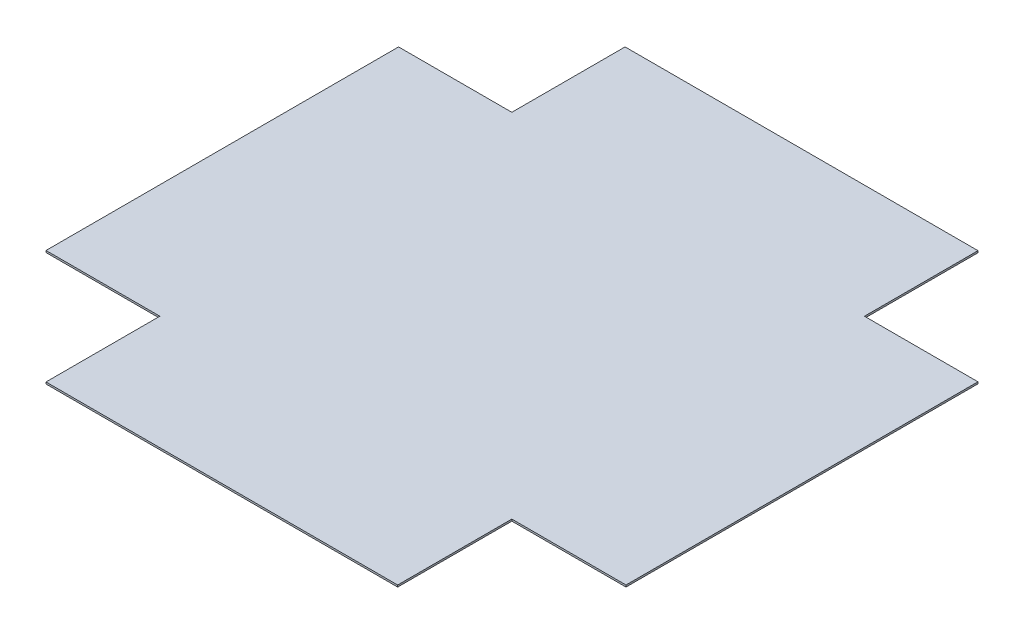
SolidWorks part; units mm, degrees
ref_plane "Front Plane" through (0, 0, 0) normal (0, 0, 1) x (1, 0, 0)
ref_plane "Top Plane" through (0, 0, 0) normal (0, 1, 0) x (1, 0, 0)
ref_plane "Right Plane" through (0, 0, 0) normal (1, 0, 0) x (0, 0, -1)
sketch "Sketch1" plane through (0, 0, 0) normal (0, 1, 0) x (1, 0, 0)
  line L1 (-355.6, 355.6) -> (355.6, 355.6)
  line L2 (-355.6, 355.6) -> (-355.6, -355.6)
  line L3 (-355.6, -355.6) -> (355.6, -355.6)
  line L4 (355.6, 355.6) -> (355.6, -355.6)
  line L5 (-355.6, 355.6) -> (355.6, -355.6) construction
  line L6 (-355.6, -355.6) -> (355.6, 355.6) construction
  point P0 (0, 0)
  dimension "D1" = 90
extrude "Boss-Extrude1" add sketch "Sketch1" along normal blind 2.2528
sketch "Sketch2" plane through (0, 0, 0) normal (0, -1, 0) x (1, 0, 0)
  line L0 (-425.4495, 425.4495) -> (-285.7495, 285.7495) construction
  line L5 (-355.6, 355.6) -> (-215.9, 355.6)
  line L6 (-355.6, 355.6) -> (-355.6, 215.9)
  line L7 (-355.6, 215.9) -> (-215.9, 215.9)
  line L8 (-215.9, 355.6) -> (-215.9, 215.9)
  line L9 (-355.6, 355.6) -> (-215.9, 215.9) construction
  line L10 (-355.6, 215.9) -> (-215.9, 355.6) construction
  point P0 (-285.75, 285.75)
  point P5 (-285.168, 285.5031)
  point P6 (0, 0)
  point P7 (0, 0)
  point P10 (0, 0)
extrude "Cut-Extrude2" cut sketch "Sketch2" against normal blind 67.2381
sketch "Sketch3" plane through (0, 2.2528, 0) normal (0, 1, 0) x (1, 0, 0)
  line L1 (215.5457, -215.5195) -> (355.6, -215.5195)
  line L2 (215.5457, -215.5195) -> (215.5457, -355.6)
  line L3 (215.5457, -355.6) -> (355.6, -355.6)
  line L4 (355.6, -215.5195) -> (355.6, -355.6)
  line L5 (215.5457, -215.5195) -> (355.6, -355.6) construction
  line L6 (215.5457, -355.6) -> (355.6, -215.5195) construction
  point P0 (285.5728, -285.5597)
  point P5 (285.3957, -285.3695)
  point P6 (355.6, -355.6)
extrude "Cut-Extrude3" cut sketch "Sketch3" against normal blind 67.2381
sketch "Sketch4" plane through (0, 2.2528, 0) normal (0, 1, 0) x (1, 0, 0)
  line L1 (-355.6, 355.6) -> (-216.6584, 355.6)
  line L2 (-355.6, 355.6) -> (-355.6, 216.6584)
  line L3 (-355.6, 216.6584) -> (-216.6584, 216.6584)
  line L4 (-216.6584, 355.6) -> (-216.6584, 216.6584)
  line L5 (-355.6, 355.6) -> (-216.6584, 216.6584) construction
  line L6 (-355.6, 216.6584) -> (-216.6584, 355.6) construction
  point P0 (-286.1292, 286.1292)
  point P5 (-286.5084, 284.8329)
  point P6 (-355.6, 355.6)
  dimension "D1" = 90
extrude "Cut-Extrude4" cut sketch "Sketch4" against normal blind 67.2381
sketch "Sketch5" plane through (0, 2.2528, 0) normal (0, 1, 0) x (1, 0, 0)
  line L1 (216.3285, 355.6) -> (355.6, 355.6)
  line L2 (216.3285, 355.6) -> (216.3285, 216.2632)
  line L3 (216.3285, 216.2632) -> (355.6, 216.2632)
  line L4 (355.6, 355.6) -> (355.6, 216.2632)
  line L5 (216.3285, 355.6) -> (355.6, 216.2632) construction
  line L6 (216.3285, 216.2632) -> (355.6, 355.6) construction
  point P0 (285.9643, 285.9316)
  point P5 (286.1785, 286.1132)
  point P6 (355.6, 355.6)
  dimension "D1" = 90
extrude "Cut-Extrude5" cut sketch "Sketch5" against normal blind 67.2381
